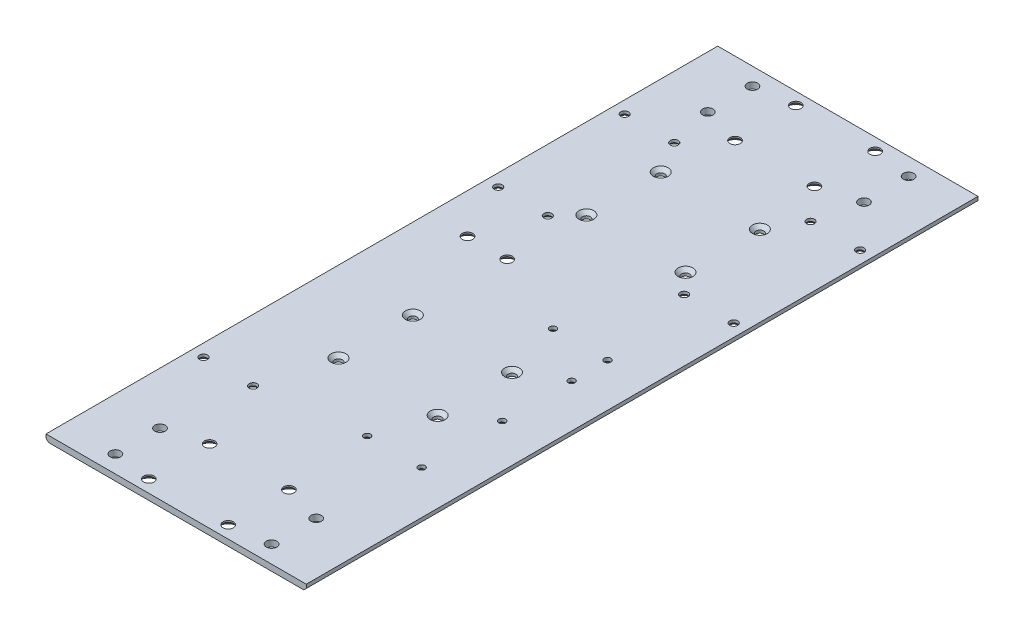
SolidWorks part; units mm, degrees
ref_plane "前视基准面" through (0, 0, 0) normal (0, 0, 1) x (1, 0, 0)
ref_plane "上视基准面" through (0, 0, 0) normal (0, 1, 0) x (1, 0, 0)
ref_plane "右视基准面" through (0, 0, 0) normal (1, 0, 0) x (0, 0, -1)
sketch "草图1" plane through (0, 0, 0) normal (0, 1, 0) x (1, 0, 0)
  line L6 (-52.5, -135.5) -> (52.5, -135.5)
  line L7 (52.5, -135.5) -> (52.5, 135.5)
  line L8 (-52.5, 135.5) -> (52.5, 135.5)
  line L9 (-52.5, -135.5) -> (-52.5, 135.5)
  circle A0 centre (16, -130.5) radius 2.1
  circle A1 centre (-16, -130.5) radius 2.1
  circle A2 centre (16, 130.5) radius 2.1
  circle A3 centre (-16, 130.5) radius 2.1
  point P8 (-50, 0)
extrude "凸台-拉伸1" add sketch "草图1" along normal blind 2.5
sketch "草图2" plane through (0, 2.5, 0) normal (0, 1, 0) x (1, 0, 0)
  line L0 (0, -1.375) -> (0, 1.375) construction
  line L1 (-1.375, 0) -> (1.375, 0) construction
  circle A0 centre (47.5, 41.95) radius 1.6
  circle A1 centre (27.5, 41.95) radius 1.6
  circle A2 centre (47.5, 92.95) radius 1.6
  circle A3 centre (27.5, 92.95) radius 1.6
  circle A4 centre (-27.5, 41.95) radius 1.6
  circle A5 centre (-47.5, 41.95) radius 1.6
  circle A6 centre (-47.5, 92.95) radius 1.6
  circle A7 centre (-27.5, 92.95) radius 1.6
  circle A10 centre (-27.5, -76.95) radius 1.6
  circle A11 centre (-47.5, -76.95) radius 1.6
  circle A12 centre (-36.5, 18.55) radius 2.1
  circle A13 centre (-20.5, 18.55) radius 2.1
  circle A14 centre (35, 3.55) radius 1.35
  circle A15 centre (13, 3.55) radius 1.35
  circle A16 centre (35, -10.95) radius 1.35
  circle A17 centre (35, -38.95) radius 1.35
  circle A18 centre (35, -71.45) radius 1.35
  circle A19 centre (13, -71.45) radius 1.35
  circle A20 centre (-16, 106) radius 2.1
  circle A21 centre (16, 106) radius 2.1
  circle A22 centre (-16, -106) radius 2.1
  circle A23 centre (16, -106) radius 2.1
  circle A24 centre (31.5, -110.5) radius 2.1
  circle A25 centre (31.5, -128.5) radius 2.1
  circle A26 centre (-31.5, -128.5) radius 2.1
  circle A27 centre (-31.5, -110.5) radius 2.1
  circle A28 centre (-31.5, 110.5) radius 2.1
  circle A29 centre (-31.5, 128.5) radius 2.1
  circle A30 centre (31.5, 128.5) radius 2.1
  circle A31 centre (31.5, 110.5) radius 2.1
  circle A32 centre (20, -20) radius 1.6
  circle A33 centre (-20, -20) radius 1.6
  circle A34 centre (20, -50) radius 1.6
  circle A35 centre (-20, -50) radius 1.6
  circle A36 centre (-20, 50) radius 1.6
  circle A37 centre (20, 50) radius 1.6
  circle A40 centre (-20, 80) radius 1.6
  circle A41 centre (20, 80) radius 1.6
  point P83 (0, 0)
  dimension "D1" = 2
  dimension "D2" = 2
extrude "切除-拉伸1" cut sketch "草图2" against normal blind 10
chamfer "倒角1" distance 1.9 angle 45 10 edges at (-16, 0, 103.9) (-16, 0, 128.4) (16, 0, 132.6) (16, 0, 103.9) (16, 0, -108.1) (-16, 0, -108.1) (-16, 0, -128.4) (16, 0, -132.6) (-20.5, 0, -20.65) (-36.5, 0, -20.65)
chamfer "倒角2" distance 1.4 angle 45 10 edges at (-47.5, 0, 75.35) (-27.5, 0, 75.35) (27.5, 0, -43.55) (47.5, 0, -43.55) (47.5, 0, -94.55) (27.5, 0, -94.55) (-47.5, 0, -94.55) (-27.5, 0, -94.55) (-47.5, 0, -43.55) (-27.5, 0, -43.55)
chamfer "倒角3" distance 1.15 angle 45 6 edges at (13, 0, -4.9) (35, 0, -4.9) (35, 0, 9.6) (35, 0, 37.6) (35, 0, 70.1) (13, 0, 70.1)
chamfer "倒角4" distance 1.4 angle 45 8 edges at (-20, 2.5, 48.4) (-20, 2.5, 18.4) (20, 2.5, 51.6) (20, 2.5, 21.6) (-20, 2.5, -48.4) (-20, 2.5, -78.4) (20, 2.5, -51.6) (20, 2.5, -81.6)
chamfer "倒角5" distance 1 angle 45 2 edges at (52.5, 0, 0) (-52.5, 0, 0)
